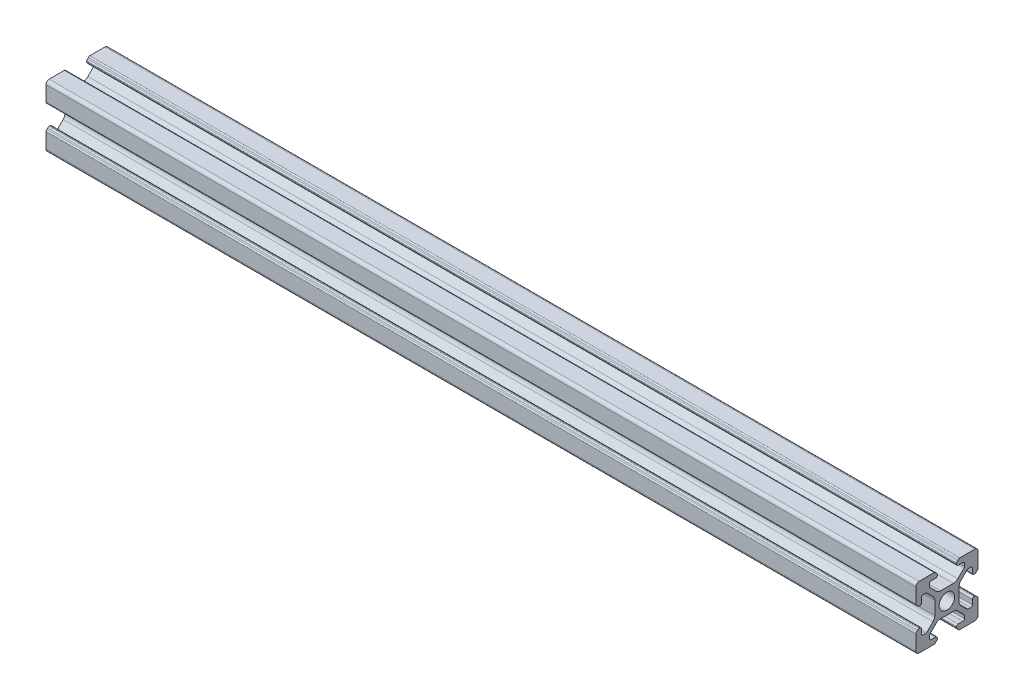
SolidWorks part; units mm, degrees
ref_plane "Front Plane" through (0, 0, 0) normal (0, 0, 1) x (1, 0, 0)
ref_plane "Top Plane" through (0, 0, 0) normal (0, 1, 0) x (1, 0, 0)
ref_plane "Right Plane" through (0, 0, 0) normal (1, 0, 0) x (0, 0, -1)
sketch "Sketch1" plane through (0, 0, 0) normal (1, 0, 0) x (0, 0, -1)
  line L0 (10, 10) -> (-10, -10) construction
  line L1 (-10, 10) -> (10, 10)
  line L2 (-10, 10) -> (-10, -10)
  line L3 (-10, -10) -> (10, -10)
  line L4 (10, 10) -> (10, -10)
  dimension "D1" = 20
extrude "Boss-Extrude1" add sketch "Sketch1" along normal blind 280
fillet "Fillet1" radius 1 4 edges at (140, -10, -10) (140, -10, 10) (140, 10, -10) (140, 10, 10)
sketch "Sketch3" plane through (0, 0, 0) normal (-1, 0, 0) x (0, 0, 1)
  line L0 (-3.6, 10) -> (3.6, 10)
  line L1 (-9, 10) -> (9, 10) construction
  line L2 (3.6, 10) -> (3.6, 9.5)
  line L3 (3.6, 9.5) -> (3.1, 9.5)
  line L4 (3.1, 9.5) -> (3.1, 8.2)
  line L5 (3.1, 8.2) -> (5.63, 8.2)
  line L6 (5.63, 8.2) -> (5.63, 6.6199)
  line L7 (5.63, 6.6199) -> (2.9101, 3.9)
  line L8 (2.9101, 3.9) -> (-2.9101, 3.9)
  line L9 (-2.9101, 3.9) -> (-5.63, 6.6199)
  line L10 (-5.63, 6.6199) -> (-5.63, 8.2)
  line L11 (-5.63, 8.2) -> (-3.1, 8.2)
  line L12 (-3.1, 8.2) -> (-3.1, 9.5)
  line L13 (-3.1, 9.5) -> (-3.6, 9.5)
  line L14 (-3.6, 9.5) -> (-3.6, 10)
  line L15 (0, 10) -> (0, 3.9) construction
  line L16 (10, 3.6) -> (10, -3.6)
  line L17 (10, -3.6) -> (9.5, -3.6)
  line L18 (9.5, -3.6) -> (9.5, -3.1)
  line L19 (9.5, -3.1) -> (8.2, -3.1)
  line L20 (8.2, -3.1) -> (8.2, -5.63)
  line L21 (8.2, -5.63) -> (6.6199, -5.63)
  line L22 (6.6199, -5.63) -> (3.9, -2.9101)
  line L23 (3.9, -2.9101) -> (3.9, 2.9101)
  line L24 (3.9, 2.9101) -> (6.6199, 5.63)
  line L25 (6.6199, 5.63) -> (8.2, 5.63)
  line L26 (8.2, 5.63) -> (8.2, 3.1)
  line L27 (8.2, 3.1) -> (9.5, 3.1)
  line L28 (9.5, 3.1) -> (9.5, 3.6)
  line L29 (9.5, 3.6) -> (10, 3.6)
  line L30 (10, 0) -> (3.9, 0) construction
  line L31 (3.6, -10) -> (-3.6, -10)
  line L32 (-3.6, -10) -> (-3.6, -9.5)
  line L33 (-3.6, -9.5) -> (-3.1, -9.5)
  line L34 (-3.1, -9.5) -> (-3.1, -8.2)
  line L35 (-3.1, -8.2) -> (-5.63, -8.2)
  line L36 (-5.63, -8.2) -> (-5.63, -6.6199)
  line L37 (-5.63, -6.6199) -> (-2.9101, -3.9)
  line L38 (-2.9101, -3.9) -> (2.9101, -3.9)
  line L39 (2.9101, -3.9) -> (5.63, -6.6199)
  line L40 (5.63, -6.6199) -> (5.63, -8.2)
  line L41 (5.63, -8.2) -> (3.1, -8.2)
  line L42 (3.1, -8.2) -> (3.1, -9.5)
  line L43 (3.1, -9.5) -> (3.6, -9.5)
  line L44 (3.6, -9.5) -> (3.6, -10)
  line L45 (0, -10) -> (0, -3.9) construction
  line L46 (-10, -3.6) -> (-10, 3.6)
  line L47 (-10, 3.6) -> (-9.5, 3.6)
  line L48 (-9.5, 3.6) -> (-9.5, 3.1)
  line L49 (-9.5, 3.1) -> (-8.2, 3.1)
  line L50 (-8.2, 3.1) -> (-8.2, 5.63)
  line L51 (-8.2, 5.63) -> (-6.6199, 5.63)
  line L52 (-6.6199, 5.63) -> (-3.9, 2.9101)
  line L53 (-3.9, 2.9101) -> (-3.9, -2.9101)
  line L54 (-3.9, -2.9101) -> (-6.6199, -5.63)
  line L55 (-6.6199, -5.63) -> (-8.2, -5.63)
  line L56 (-8.2, -5.63) -> (-8.2, -3.1)
  line L57 (-8.2, -3.1) -> (-9.5, -3.1)
  line L58 (-9.5, -3.1) -> (-9.5, -3.6)
  line L59 (-9.5, -3.6) -> (-10, -3.6)
  line L60 (-10, 0) -> (-3.9, 0) construction
  line L61 (10, 9) -> (10, -9) construction
  line L62 (-10, -9) -> (-10, 9) construction
  point P4 (0, 10)
  point P17 (0, 0)
  point P26 (10, 0)
  point P43 (0, -10)
  point P60 (-10, 0)
  point P75 (0, 0)
  dimension "D1" = 135
  dimension "D2" = 6.2
  dimension "D3" = 7.2
  dimension "D4" = 6.1
  dimension "D5" = 11.26
  dimension "D6" = 0.5
  dimension "D8" = 1.4
  dimension "D9" = 1.8
  dimension "D7" = 4
extrude "Cut-Extrude1" cut sketch "Sketch3" against normal through all
hole_wizard "Ø5.0 (5) Diameter Hole1" positions "Sketch4" profile "Sketch5" hole size "Ø5.0" standard "ANSI Metric" end condition through all
sketch "Sketch4" plane through (0, 0, 0) normal (-1, 0, 0) x (0, 0, 1)
  point P0 (0, 0)
sketch "Sketch5" plane through (0, 0, 0) normal (0, 1, 0) x (0, 0, 1)
  line L0 (0, 0) -> (0, 280)
  line L1 (0, 280) -> (2.5, 280)
  line L2 (2.5, 280) -> (2.5, 0)
  line L5 (2.5, 0) -> (0, 0)
  line L11 (0, -6.35) -> (0, 107.95) construction
  dimension "Thru Hole Dia." = 5
  dimension "Thru Hole Depth" = 280
fillet "Fillet2" radius 2 8 edges at (140, -3.9, -2.9101) (140, -3.9, 2.9101) (140, -2.9101, 3.9) (140, 2.9101, 3.9) (140, 3.9, 2.9101) (140, 3.9, -2.9101) (140, 2.9101, -3.9) (140, -2.9101, -3.9)
fillet "Fillet3" radius 0.5 20 edges at (140, 3.6, -10) (140, 3.1, -9.5) (140, 3.1, -8.2) (140, 5.63, -8.2) (140, 5.63, -6.6199) (140, 3.6, 10) (140, 3.1, 9.5) (140, 3.1, 8.2) (140, 5.63, 8.2) (140, 5.63, 6.6199) (140, 6.6199, 5.63) (140, 8.2, 5.63) (140, 8.2, 3.1) (140, 9.5, 3.1) (140, 10, 3.6) (140, 9.5, -3.1) (140, 10, -3.6) (140, 8.2, -3.1) (140, 8.2, -5.63) (140, 6.6199, -5.63)
fillet "Fillet4" radius 0.5 20 edges at (140, -3.6, 10) (140, -3.1, 9.5) (140, -3.1, 8.2) (140, -5.63, 8.2) (140, -5.63, 6.6199) (140, -6.6199, 5.63) (140, -8.2, 5.63) (140, -8.2, 3.1) (140, -10, 3.6) (140, -9.5, 3.1) (140, -10, -3.6) (140, -9.5, -3.1) (140, -8.2, -3.1) (140, -8.2, -5.63) (140, -6.6199, -5.63) (140, -5.63, -6.6199) (140, -5.63, -8.2) (140, -3.1, -8.2) (140, -3.1, -9.5) (140, -3.6, -10)
fillet "Fillet5" radius 0.5 8 edges at (140, 3.6, -9.5) (140, -3.6, -9.5) (140, -9.5, -3.6) (140, -9.5, 3.6) (140, -3.6, 9.5) (140, 3.6, 9.5) (140, 9.5, 3.6) (140, 9.5, -3.6)
